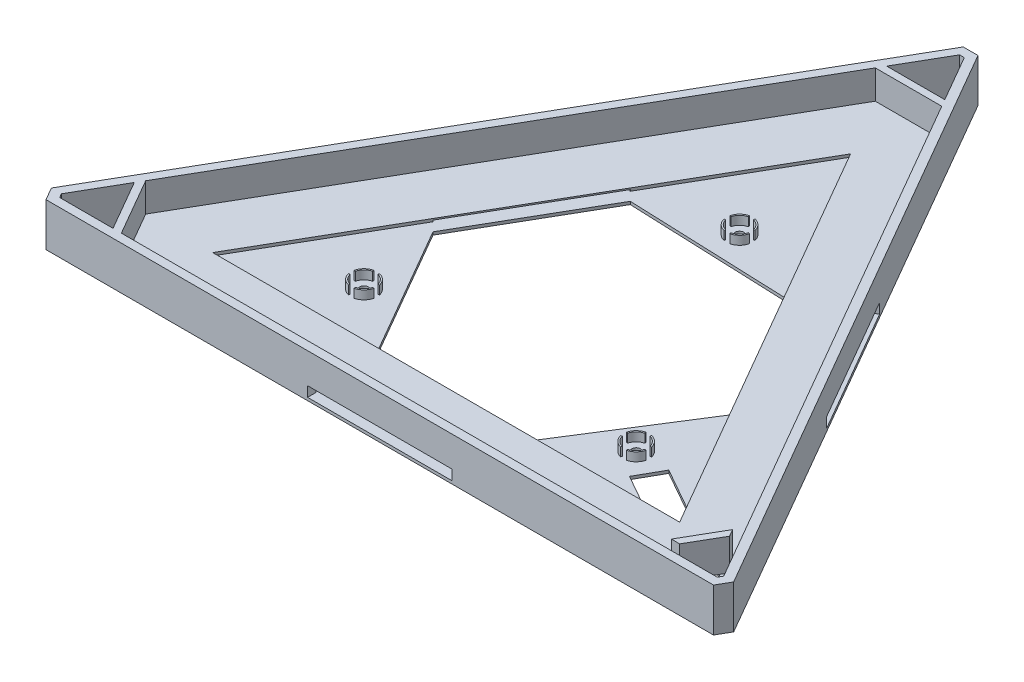
SolidWorks part; units mm, degrees
ref_plane "Front Plane" through (0, 0, 0) normal (0, 0, 1) x (1, 0, 0)
ref_plane "Top Plane" through (0, 0, 0) normal (0, 1, 0) x (1, 0, 0)
ref_plane "Right Plane" through (0, 0, 0) normal (1, 0, 0) x (0, 0, -1)
sketch "Sketch1" plane through (0, 0, 0) normal (0, 1, 0) x (1, 0, 0)
  line L0 (351.2729, 67.6655) -> (468.273, -134.9846)
  line L1 (347.2728, 67.6655) -> (347.2728, 65.1655) construction
  line L2 (409.773, -33.6595) -> (407.6079, -34.9095) construction
  line L3 (468.273, -134.9846) -> (464.2732, -141.9124)
  line L4 (230.2733, -141.9124) -> (464.2732, -141.9124)
  line L5 (230.2733, -141.9124) -> (226.2727, -134.9842)
  line L6 (226.2727, -134.9842) -> (343.2728, 67.6655)
  line L7 (353.4142, 63.9567) -> (351.2491, 62.7067) construction
  line L8 (347.2733, -141.9124) -> (347.2733, -139.4124) construction
  line L9 (231.7167, -139.4124) -> (462.8299, -139.4124)
  line L10 (284.7727, -33.6594) -> (286.9378, -34.9094) construction
  line L11 (344.7161, 65.1655) -> (349.8295, 65.1655)
  line L12 (465.3862, -134.9846) -> (349.8295, 65.1655)
  line L13 (466.2731, -138.4485) -> (464.1081, -137.1985) construction
  line L14 (462.8299, -139.4124) -> (465.3862, -134.9846)
  line L15 (229.1594, -134.9842) -> (344.7161, 65.1655)
  line L16 (229.1594, -134.9842) -> (231.7167, -139.4124)
  line L17 (286.9378, -34.9094) -> (287.3708, -35.1594) construction
  line L18 (230.438, -137.1983) -> (230.871, -136.9483) construction
  line L19 (232.0053, -138.9123) -> (229.7368, -134.9842)
  line L20 (343.2728, 67.6655) -> (351.2729, 67.6655)
  line L21 (345.0048, 64.6655) -> (229.7368, -134.9842)
  line L22 (349.5409, 64.6655) -> (345.0048, 64.6655)
  line L23 (249.0568, -126.4468) -> (246.8918, -127.697) construction
  line L24 (407.6079, -34.9095) -> (407.1749, -35.1595) construction
  line L26 (233.4463, -136.4089) -> (251.9226, -136.4093)
  line L27 (464.8089, -134.9846) -> (462.5412, -138.9123)
  line L28 (462.5412, -138.9123) -> (232.0053, -138.9123)
  line L29 (251.9226, -136.4093) -> (241.8609, -118.9847)
  line L30 (241.8609, -118.9847) -> (232.6236, -134.9842)
  line L31 (232.6236, -134.9842) -> (233.4463, -136.4089)
  line L33 (287.3708, -35.1594) -> (289.5359, -36.4094) construction
  line L34 (254.8093, -136.4089) -> (243.3042, -116.4848)
  line L35 (335.7675, 43.666) -> (243.3042, -116.4848)
  line L36 (358.7782, 43.666) -> (335.7675, 43.666)
  line L38 (289.5359, -36.4094) -> (306.8564, -46.4094) construction
  line L41 (461.939, -134.9846) -> (461.1164, -136.4093)
  line L42 (347.2688, -136.4172) -> (347.2688, -116.4172) construction
  line L43 (442.6021, -136.4093) -> (452.6999, -118.9847)
  line L44 (245.2636, -119.878) -> (249.0568, -126.4468) construction
  line L45 (452.6999, -118.9847) -> (461.939, -134.9846)
  line L48 (461.1164, -136.4093) -> (442.6021, -136.4093)
  line L49 (405.0134, -36.4027) -> (387.6936, -46.404) construction
  line L50 (306.8564, -46.4094) -> (466.2731, -138.4485) construction
  line L51 (357.3348, 46.166) -> (337.2109, 46.166)
  line L52 (337.2109, 46.166) -> (346.4484, 62.1659)
  line L53 (346.4484, 62.1659) -> (348.0966, 62.164)
  line L54 (348.0966, 62.164) -> (357.3348, 46.166)
  line L55 (228.273, -138.4483) -> (387.6936, -46.404) construction
  line L56 (347.2688, -116.4172) -> (347.2728, 43.666) construction
  line L57 (266.4391, -116.428) -> (428.1137, -116.4172)
  line L58 (347.2736, 23.6092) -> (428.1137, -116.4172)
  line L59 (266.4391, -116.428) -> (347.2736, 23.6092)
  line L60 (439.7283, -136.4254) -> (439.7283, -132.9254) construction
  line L61 (451.2487, -116.4715) -> (448.6507, -117.9717) construction
  line L62 (452.6999, -118.9847) -> (358.7782, 43.666)
  line L63 (442.6021, -136.4093) -> (254.8093, -136.4089)
  line L64 (441.749, -132.9254) -> (444.621, -132.9254)
  line L65 (448.6507, -117.9717) -> (450.9647, -121.979) construction
  line L66 (449.5167, -119.4714) -> (450.9647, -121.979)
  line L67 (441.749, -132.9254) -> (449.5167, -119.4714)
  line L68 (450.9647, -121.979) -> (444.621, -132.9254)
  point P13 (407.6079, -34.9095)
  point P20 (464.1081, -137.1985)
  point P23 (347.2733, -139.4124)
  point P25 (347.2732, -141.9124)
  point P27 (347.2728, 65.1655)
  point P31 (286.9378, -34.9094)
  point P37 (287.3708, -35.1594)
  point P39 (230.871, -136.9483)
  point P41 (347.2728, 64.6655)
  point P45 (407.1749, -35.1595)
  point P50 (246.8918, -127.697)
  point P56 (289.5359, -36.4094)
  point P58 (249.0568, -126.4468)
  point P60 (347.2728, 43.666)
  point P62 (345.0048, -136.4089)
  point P64 (445.4885, -126.4485)
  point P71 (447.651, -127.697)
  point P77 (347.2728, 46.166)
  point P84 (347.2688, -116.4172)
  point P87 (387.6936, -46.404)
  point P89 (306.8564, -46.4094)
  point P100 (405.0134, -36.4027)
  dimension "D1" = 2.5
  dimension "D2" = 2.5
  dimension "D3" = 2.5
  dimension "D4" = 2.5
  dimension "D5" = 2.5
  dimension "D6" = 2.5
  dimension "D7" = 0.5
  dimension "D8" = 0.5
  dimension "D9" = 0.5
  dimension "D10" = 2.5
  dimension "D11" = 2.5
  dimension "D12" = 20
  dimension "D13" = 20
  dimension "D14" = 20
  dimension "D15" = 3.5
  dimension "D16" = 3
extrude "Boss-Extrude1" add sketch "Sketch1" along normal blind 1 contours L36 L35 L34 L57 L59 L58 region at (251.4484, 0, 125.0658)
extrude "Boss-Extrude2" add sketch "Sketch1<9>" along normal blind 11 contours L28 L27 L22 L21 L19 L31 L30 L29 L26 L34 L35 L36 L41 L48 L43 L45 L53 L54 L51 L52 | L68 L64 L67 L66 region at (230.7087, 0, 137.042)
sketch "Sketch1<9>" plane through (0, 0, 0) normal (0, 1, 0) x (1, 0, 0) same geometry as "Sketch1"
extrude "Boss-Extrude3" add sketch "Sketch1<10>" along normal blind 5 and the other way blind 3 contours L28 L27 L22 L21 L19 L31 L30 L29 L26 L34 L35 L36 L41 L48 L43 L45 L53 L54 L51 L52 region at (230.7087, 0, 137.042)
sketch "Sketch1<10>" plane through (0, 0, 0) normal (0, 1, 0) x (1, 0, 0) same geometry as "Sketch1"
sketch "Sketch3" plane through (290.5896, 0, -167.772) normal (0.866, 0, -0.5) x (-0.5, 0, -0.866)
  line L1 (-261.593, -6.5) -> (-211.593, -6.5)
  line L2 (-261.593, -6.5) -> (-261.593, 0.5)
  line L3 (-261.593, 0.5) -> (-211.593, 0.5)
  line L4 (-211.593, -6.5) -> (-211.593, 0.5)
  line L5 (-261.593, -6.5) -> (-211.593, 0.5) construction
  line L6 (-261.593, 0.5) -> (-211.593, -6.5) construction
  point P0 (-236.593, -3)
  dimension "D1" = 50
  dimension "D2" = 7
extrude "Cut-Extrude3" cut sketch "Sketch3" against normal blind 25
sketch "Sketch5" plane through (0, 0, 139.4124) normal (0, 0, 1) x (1, 0, 0)
  line L0 (231.7167, -3) -> (462.8299, -3) construction
  line L1 (322.2733, -6.5) -> (372.2733, -6.5)
  line L2 (322.2733, -6.5) -> (322.2733, 0.5)
  line L3 (322.2733, 0.5) -> (372.2733, 0.5)
  line L4 (372.2733, -6.5) -> (372.2733, 0.5)
  line L5 (322.2733, -6.5) -> (372.2733, 0.5) construction
  line L6 (322.2733, 0.5) -> (372.2733, -6.5) construction
  point P0 (347.2733, -3)
  dimension "D1" = 50
  dimension "D2" = 7
extrude "Cut-Extrude4" cut sketch "Sketch5" against normal blind 25
sketch "Sketch6" plane through (230.3194, 0, 132.9752) normal (-0.866, 0, -0.5) x (-0.5, 0, 0.866)
  line L0 (2.3199, -3) -> (-228.7932, -3) construction
  line L1 (-138.2367, -6.5) -> (-88.2367, -6.5)
  line L2 (-138.2367, -6.5) -> (-138.2367, 0.5)
  line L3 (-138.2367, 0.5) -> (-88.2367, 0.5)
  line L4 (-88.2367, -6.5) -> (-88.2367, 0.5)
  line L5 (-138.2367, -6.5) -> (-88.2367, 0.5) construction
  line L6 (-138.2367, 0.5) -> (-88.2367, -6.5) construction
  point P0 (-113.2367, -3)
  dimension "D1" = 50
  dimension "D2" = 7
extrude "Cut-Extrude5" cut sketch "Sketch6" against normal blind 25
sketch "Sketch8" plane through (0, -3, 0) normal (0, -1, 0) x (1, 0, 0)
  line L1 (349.8295, -65.1655) -> (465.3862, 134.9846)
  line L2 (465.3862, 134.9846) -> (462.8299, 139.4124)
  line L6 (462.8299, 139.4124) -> (231.7167, 139.4124)
  line L7 (450.147, 123.2807) -> (452.6999, 118.9847)
  line L9 (452.6999, 118.9847) -> (461.939, 134.9846)
  line L12 (461.939, 134.9846) -> (461.1164, 136.4093)
  line L17 (461.1164, 136.4093) -> (442.6021, 136.4093)
  line L19 (322.2733, 116.4243) -> (294.3582, 68.0611)
  line L20 (294.3582, 68.0611) -> (319.3545, 24.7577)
  line L21 (319.3545, 24.7577) -> (376.4737, 26.9694)
  line L22 (376.4737, 26.9694) -> (401.4727, 70.2712)
  line L23 (401.4727, 70.2712) -> (372.2733, 116.4209)
  line L24 (372.2733, 116.4209) -> (322.2733, 116.4243)
  line L25 (386.873, 93.3461) -> (395.3235, 98.6928) construction
  line L30 (308.3157, 92.2427) -> (299.6549, 97.2417) construction
  line L31 (347.9141, 25.8635) -> (348.3013, 15.8635) construction
  line L34 (401.698, 107.3846) -> (445.2267, 131.9864)
  line L35 (450.147, 123.2807) -> (406.6183, 98.6788)
  line L36 (401.698, 107.3846) -> (406.6183, 98.6788)
  line L37 (231.7167, 139.4124) -> (229.1594, 134.9842)
  line L39 (233.4463, 136.4089) -> (251.9226, 136.4093)
  line L40 (251.9226, 136.4093) -> (241.8609, 118.9847)
  line L41 (241.8609, 118.9847) -> (232.6236, 134.9842)
  line L42 (232.6236, 134.9842) -> (233.4463, 136.4089)
  line L43 (349.8295, -65.1655) -> (344.7161, -65.1655)
  line L44 (344.7161, -65.1655) -> (229.1594, 134.9842)
  line L45 (337.2109, -46.166) -> (357.3348, -46.166)
  line L46 (357.3348, -46.166) -> (348.0966, -62.164)
  line L47 (348.0966, -62.164) -> (346.4484, -62.1659)
  line L48 (346.4484, -62.1659) -> (337.2109, -46.166)
  line L49 (442.6021, 136.4093) -> (445.2267, 131.9864)
  circle A0 centre (395.3235, 98.6928) radius 1.5
  circle A1 centre (348.3013, 15.8635) radius 1.5
  circle A2 centre (299.6549, 97.2417) radius 1.5
  dimension "D6" = 3
  dimension "D7" = 3
  dimension "D8" = 3
  dimension "D1" = 10
  dimension "D2" = 50
  dimension "D3" = 10
  dimension "D4" = 10
  dimension "D5" = 10
extrude "Boss-Extrude5" add sketch "Sketch8" along normal blind 1
sketch "Sketch12" plane through (0, -3, 0) normal (0, 1, 0) x (1, 0, 0)
  line L0 (348.3013, -11.8635) -> (348.3013, -11.3635) construction
  line L1 (348.3013, -11.3635) -> (349.2951, -11.4746) construction
  line L2 (349.2951, -11.4746) -> (349.1847, -11.9623)
  line L3 (348.3013, -11.3635) -> (347.3075, -11.4746) construction
  line L4 (347.3075, -11.4746) -> (347.4179, -11.9623)
  line L5 (352.3013, -15.8635) -> (352.8013, -15.8635) construction
  line L6 (344.3013, -15.8635) -> (343.8013, -15.8635) construction
  line L7 (348.3013, -19.8635) -> (348.3013, -20.3635) construction
  line L8 (352.8013, -15.8635) -> (352.6902, -14.8697) construction
  line L9 (352.8013, -15.8635) -> (352.6902, -16.8573) construction
  line L10 (343.8013, -15.8635) -> (343.9124, -14.8697) construction
  line L11 (343.8013, -15.8635) -> (343.9124, -16.8573) construction
  line L12 (348.3013, -20.3635) -> (349.2951, -20.2524) construction
  line L13 (348.3013, -20.3635) -> (347.3075, -20.2524) construction
  line L14 (343.9124, -14.8697) -> (348.3013, -15.8635) construction
  line L15 (348.3013, -15.8635) -> (352.6902, -14.8697) construction
  line L16 (343.9124, -16.8573) -> (348.3013, -15.8635) construction
  line L17 (348.3013, -15.8635) -> (352.6902, -16.8573) construction
  line L18 (347.3075, -20.2524) -> (348.3013, -15.8635) construction
  line L19 (348.3013, -15.8635) -> (349.2951, -20.2524) construction
  line L20 (343.9124, -14.8697) -> (344.4001, -14.9801)
  line L21 (343.9124, -16.8573) -> (344.4001, -16.7469)
  line L22 (347.3075, -20.2524) -> (347.4179, -19.7648)
  line L23 (349.2951, -20.2524) -> (349.1847, -19.7648)
  line L24 (352.6902, -14.8697) -> (352.2025, -14.9801)
  line L25 (352.6902, -16.8573) -> (352.2025, -16.7469)
  line L26 (395.3235, -94.1928) -> (395.3235, -98.6928) construction
  line L27 (395.3235, -98.6928) -> (390.8235, -98.6928) construction
  line L28 (390.8235, -98.6928) -> (390.9347, -97.699) construction
  line L29 (399.8235, -98.6928) -> (395.3235, -98.6928) construction
  line L30 (395.3235, -98.6928) -> (395.3235, -103.1928) construction
  line L31 (395.3235, -103.1928) -> (396.3173, -103.0817) construction
  line L32 (395.3235, -94.1928) -> (396.3173, -94.3039) construction
  line L33 (395.3235, -94.1928) -> (394.3297, -94.3039) construction
  line L34 (399.7124, -97.699) -> (399.8235, -98.6928) construction
  line L35 (399.8235, -98.6928) -> (399.7124, -99.6866) construction
  line L36 (390.9347, -99.6866) -> (390.8235, -98.6928) construction
  line L37 (394.3297, -103.0817) -> (395.3235, -103.1928) construction
  line L38 (394.3297, -94.3039) -> (395.3235, -98.6928) construction
  line L39 (395.3235, -98.6928) -> (396.3173, -94.3039) construction
  line L40 (390.9347, -99.6866) -> (395.3235, -98.6928) construction
  line L41 (395.3235, -98.6928) -> (390.9347, -97.699) construction
  line L42 (399.7124, -97.699) -> (395.3235, -98.6928) construction
  line L43 (395.3235, -98.6928) -> (399.7124, -99.6866) construction
  line L44 (394.3297, -103.0817) -> (395.3235, -98.6928) construction
  line L45 (395.3235, -98.6928) -> (396.3173, -103.0817) construction
  line L46 (394.3297, -94.3039) -> (394.4402, -94.7916)
  line L47 (396.3173, -94.3039) -> (396.2069, -94.7916)
  line L48 (399.7124, -97.699) -> (399.2248, -97.8094)
  line L49 (399.7124, -99.6866) -> (399.2248, -99.5762)
  line L50 (396.3173, -103.0817) -> (396.2069, -102.5941)
  line L51 (394.3297, -103.0817) -> (394.4402, -102.5941)
  line L52 (390.9347, -99.6866) -> (391.4223, -99.5762)
  line L53 (390.9347, -97.699) -> (391.4248, -97.7985)
  line L54 (299.6549, -92.7417) -> (299.6549, -97.2417) construction
  line L55 (299.6549, -97.2417) -> (304.1549, -97.2417) construction
  line L56 (299.6549, -101.7417) -> (299.6549, -97.2417) construction
  line L57 (299.6549, -97.2417) -> (295.1549, -97.2417) construction
  line L58 (299.6549, -97.2417) -> (298.6611, -92.8528) construction
  line L59 (298.6611, -92.8528) -> (299.6549, -92.7417) construction
  line L60 (299.6549, -92.7417) -> (300.6487, -92.8528) construction
  line L61 (300.6487, -92.8528) -> (299.6549, -97.2417) construction
  line L62 (299.6549, -97.2417) -> (304.0438, -96.2479) construction
  line L63 (304.0438, -96.2479) -> (304.1549, -97.2417) construction
  line L64 (304.1549, -97.2417) -> (304.0438, -98.2355) construction
  line L65 (304.0438, -98.2355) -> (299.6549, -97.2417) construction
  line L66 (299.6549, -97.2417) -> (300.6487, -101.6306) construction
  line L67 (300.6487, -101.6306) -> (299.6549, -101.7417) construction
  line L68 (299.6549, -101.7417) -> (298.6611, -101.6306) construction
  line L69 (298.6611, -101.6306) -> (299.6549, -97.2417) construction
  line L70 (299.6549, -97.2417) -> (295.266, -98.2355) construction
  line L71 (295.266, -98.2355) -> (295.1549, -97.2417) construction
  line L72 (295.1549, -97.2417) -> (295.266, -96.2479) construction
  line L73 (295.266, -96.2479) -> (299.6549, -97.2417) construction
  line L74 (295.266, -96.2479) -> (295.7537, -96.3583)
  line L75 (295.266, -98.2355) -> (295.7537, -98.1251)
  line L76 (298.6611, -101.6306) -> (298.7715, -101.1429)
  line L77 (300.6487, -101.6306) -> (300.5383, -101.1429)
  line L78 (304.0438, -98.2355) -> (303.5561, -98.1251)
  line L79 (304.0438, -96.2479) -> (303.5561, -96.3583)
  line L80 (300.6487, -92.8528) -> (300.5383, -93.3404)
  line L81 (298.6611, -92.8528) -> (298.7715, -93.3404)
  circle A0 centre (348.3013, -15.8635) radius 4.5
  circle A1 centre (395.3235, -98.6928) radius 4.5
  circle A2 centre (299.6549, -97.2417) radius 4.5
  circle A3 centre (348.3013, -15.8635) radius 4
  circle A4 centre (395.3235, -98.6928) radius 4
  circle A5 centre (299.6549, -97.2417) radius 4
  dimension "D1" = 9
  dimension "D2" = 9
  dimension "D3" = 9
  dimension "D4" = 8
  dimension "D5" = 8
  dimension "D6" = 8
  dimension "D7" = 1
  dimension "D8" = 1
  dimension "D9" = 1
  dimension "D10" = 1
  dimension "D11" = 1
  dimension "D12" = 1
  dimension "D13" = 1
  dimension "D14" = 1
  dimension "D15" = 1
  dimension "D16" = 1
  dimension "D17" = 1
  dimension "D18" = 1
  dimension "D19" = 1
  dimension "D20" = 1
  dimension "D21" = 1
  dimension "D22" = 1
  dimension "D23" = 1
  dimension "D24" = 1
  dimension "D25" = 1
  dimension "D26" = 1
  dimension "D27" = 1
  dimension "D28" = 1
  dimension "D29" = 1
  dimension "D30" = 1
extrude "Boss-Extrude10" add sketch "Sketch12" along normal blind 3 contours A3 L4 A0 L20 | A3 L24 A0 L2 | A3 L23 A0 L25 | A3 L21 A0 L22 | A4 L46 A1 L53 | A4 L48 A1 L47 | A4 L50 A1 L49 | A4 L52 A1 L51 | A5 L81 A2 L74 | A5 L79 A2 L80 | A5 L77 A2 L78 | A5 L75 A2 L76 region at (351.1537, -3, 13.0111) region at (345.4489, -3, 13.0111) region at (351.1537, -3, 18.7159) region at (345.4489, -3, 18.7159) region at (392.4726, -3, 95.8382) region at (398.1759, -3, 95.8404) region at (392.4712, -3, 101.5452) region at (398.1759, -3, 101.5452) region at (296.8025, -3, 94.3893) region at (296.8025, -3, 100.0941) region at (302.5073, -3, 94.3893) region at (302.5073, -3, 100.0941)
